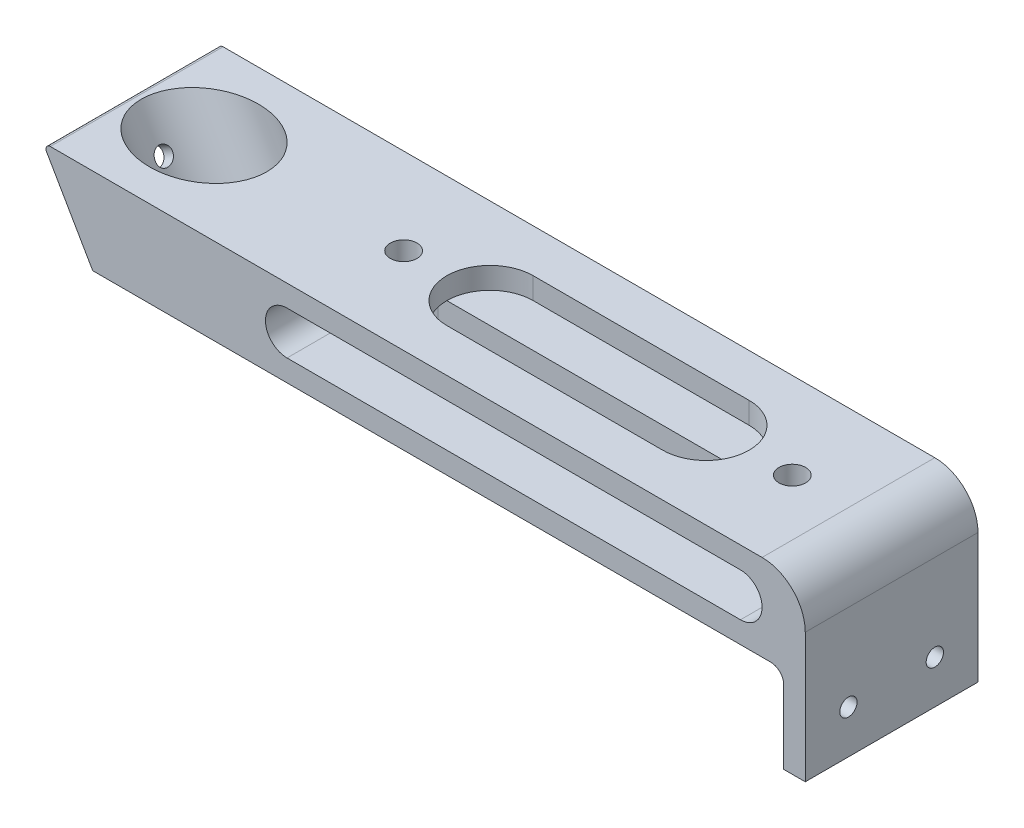
SolidWorks part; units mm, degrees
ref_plane "前视基准面" through (0, 0, 0) normal (0, 0, 1) x (1, 0, 0)
ref_plane "上视基准面" through (0, 0, 0) normal (0, 1, 0) x (1, 0, 0)
ref_plane "右视基准面" through (0, 0, 0) normal (1, 0, 0) x (0, 0, -1)
sketch "草图1" plane through (0, 0, 0) normal (0, 0, 1) x (1, 0, 0)
  line L0 (0, 0) -> (165, 0)
  line L1 (165, 0) -> (165, 20)
  line L2 (165, 20) -> (-11.547, 20)
  line L3 (-11.547, 20) -> (0, 0)
  line L4 (0, 0) -> (0, 151.1702) construction
  dimension "D1" = 30
  dimension "D2" = 20
  dimension "D3" = 165
extrude "凸台-拉伸1" add sketch "草图1" along normal blind 40
ref_plane "基准面1" through (-11.547, 20, 0) normal (-0.5, 0.866, 0) x (0, 0, -1)
sketch "草图2" plane through (-11.547, 20, 0) normal (-0.5, 0.866, 0) x (0, 0, -1)
  line L0 (0, 0) -> (-84.5846, 0) construction
  line L1 (0, -152.8942) -> (0, 0) construction
  circle A0 centre (-20, -15) radius 12.6
  dimension "D3" = 25.2
  dimension "D1" = 20
  dimension "D2" = 15
extrude "切除-拉伸1" cut sketch "草图2" against normal through all
sketch "草图3" plane through (0, 0, 0) normal (-0.866, -0.5, 0) x (0, 0, 1)
  line L0 (0, 0) -> (0, 49.6712) construction
  circle A0 centre (20, 11.4672) radius 2
  dimension "D2" = 4
  dimension "D1" = 40
extrude "切除-拉伸2" cut sketch "草图3" against normal up to next
sketch "草图4" plane through (0, 0, 0) normal (0, -1, 0) x (1, 0, 0)
  line L0 (0, 0) -> (165, 0) construction
  line L1 (165, 40) -> (160, 40)
  line L2 (165, 40) -> (165, 0)
  line L3 (165, 0) -> (160, 0)
  line L4 (160, 40) -> (160, 0)
  dimension "D1" = 5
extrude "凸台-拉伸2" add sketch "草图4" along normal blind 20
sketch "草图5" plane through (160, 0, 0) normal (-1, 0, 0) x (0, 0, 1)
  line L0 (20, 0) -> (20, -29.3991) construction
  line L1 (40, 0) -> (0, 0) construction
  line L2 (10, -10) -> (30, -10) construction
  circle A0 centre (10, -10) radius 2
  circle A1 centre (30, -10) radius 2
  dimension "D1" = 20
  dimension "D3" = 4
  dimension "D2" = 10
extrude "切除-拉伸3" cut sketch "草图5" against normal through all
fillet "圆角1" radius 10 1 edges at (165, 20, 20)
fillet "圆角2" radius 3 1 edges at (160, 0, 20)
sketch "草图6" plane through (0, 0, 0) normal (0, 0, -1) x (-1, 0, 0)
  line L0 (-150, 10) -> (-45, 10) construction
  line L1 (-150, 15) -> (-45, 15)
  line L2 (-150, 5) -> (-45, 5)
  line L3 (-155, 20) -> (11.547, 20) construction
  line L4 (-160, -20) -> (-160, -3) construction
  line L5 (0, 0) -> (0, 35.4113) construction
  arc A0 (-150, 15) -> (-150, 5) centre (-150, 10) ccw
  arc A1 (-45, 5) -> (-45, 15) centre (-45, 10) ccw
  point P2 (-97.5, 10)
  dimension "D1" = 10
  dimension "D2" = 5
  dimension "D3" = 10
  dimension "D4" = 45
extrude "切除-拉伸4" cut sketch "草图6" against normal through all
sketch "草图7" plane through (0, 0, 0) normal (0, -1, 0) x (1, 0, 0)
  line L0 (0, 20) -> (157, 20) construction
  line L1 (0, 40) -> (0, 0) construction
  line L2 (157, 0) -> (157, 40) construction
  circle A0 centre (52, 20) radius 3.1
  circle A1 centre (142, 20) radius 3.1
  dimension "D1" = 6.2
  dimension "D2" = 6.2
  dimension "D3" = 90
  dimension "D4" = 15
extrude "切除-拉伸5" cut sketch "草图7" against normal through all
sketch "草图8" plane through (0, 0, 0) normal (0, -1, 0) x (1, 0, 0)
  line L0 (55.1, 20) -> (138.9, 20) construction
  line L2 (50, 30) -> (144, 30)
  line L3 (47, 27) -> (47, 13)
  line L4 (50, 10) -> (144, 10)
  line L5 (147, 27) -> (147, 13)
  line L6 (47, 30) -> (147, 10) construction
  line L7 (47, 10) -> (147, 30) construction
  circle A0 centre (52, 20) radius 3.1 construction
  circle A1 centre (142, 20) radius 3.1 construction
  arc A2 (144, 30) -> (147, 27) centre (144, 27) cw
  arc A3 (144, 10) -> (147, 13) centre (144, 13) ccw
  arc A4 (47, 13) -> (50, 10) centre (50, 13) ccw
  arc A5 (47, 27) -> (50, 30) centre (50, 27) cw
  point P7 (97, 20)
  dimension "D3" = 3
  dimension "D1" = 20
  dimension "D2" = 100
extrude "切除-拉伸6" cut sketch "草图8" against normal up to next
fillet "圆角3" radius 1 1 edges at (-11.547, 20, 20)
sketch "草图9" plane through (0, 15, 0) normal (0, -1, 0) x (1, 0, 0)
  line L0 (122, 20) -> (72, 20) construction
  line L1 (122, 10) -> (72, 10)
  line L2 (122, 30) -> (72, 30)
  line L3 (0, 40) -> (157, 40) construction
  line L4 (147, 13) -> (147, 27) construction
  line L5 (50, 10) -> (144, 10) construction
  arc A0 (122, 10) -> (122, 30) centre (122, 20) ccw
  arc A1 (72, 30) -> (72, 10) centre (72, 20) ccw
  point P2 (97, 20)
  dimension "D1" = 20
  dimension "D2" = 50
  dimension "D3" = 50
extrude "切除-拉伸7" cut sketch "草图9" against normal up to next
